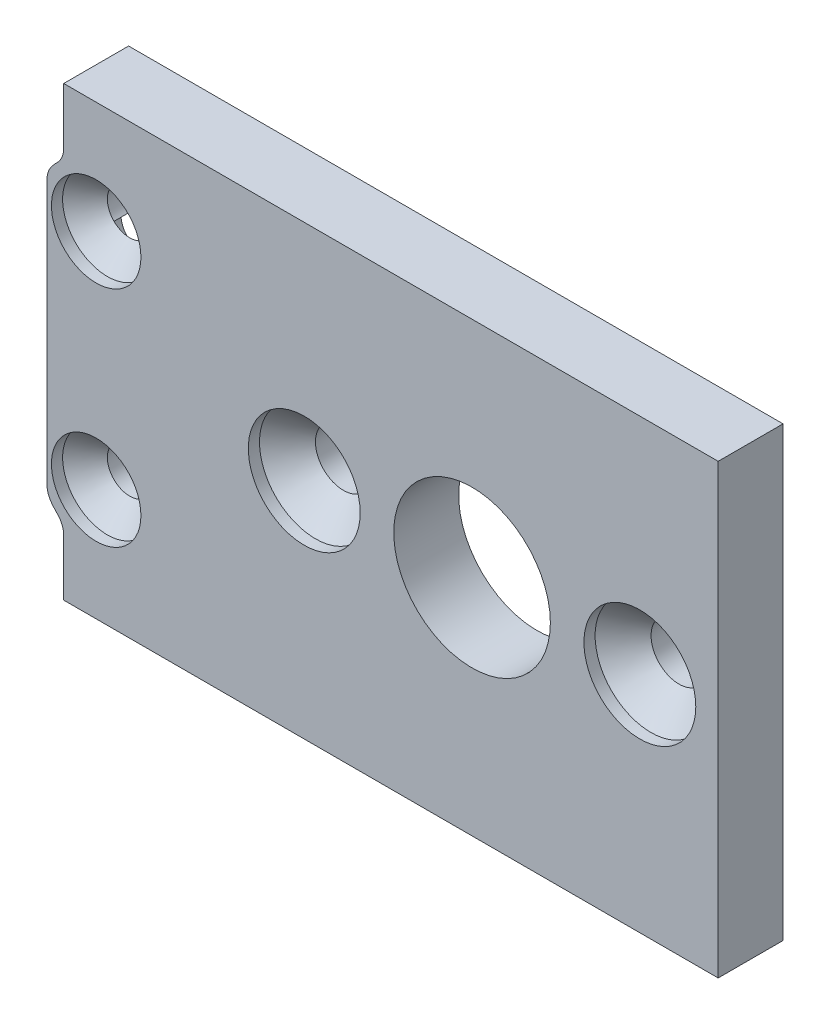
SolidWorks part; units mm, degrees
ref_plane "Front Plane" through (0, 0, 0) normal (0, 0, 1) x (1, 0, 0)
ref_plane "Top Plane" through (0, 0, 0) normal (0, 1, 0) x (1, 0, 0)
ref_plane "Right Plane" through (0, 0, 0) normal (1, 0, 0) x (0, 0, -1)
sketch "Sketch1" plane through (0, 0, 0) normal (0, 0, 1) x (1, 0, 0)
  line L1 (-92.5, 10) -> (92.5, 10)
  line L2 (-92.5, 10) -> (-92.5, -10)
  line L3 (-92.5, -10) -> (92.5, -10)
  line L4 (92.5, 10) -> (92.5, -10)
  line L5 (-92.5, 10) -> (92.5, -10) construction
  line L6 (-92.5, -10) -> (92.5, 10) construction
  point P0 (0, 0)
  dimension "D1" = 20
  dimension "D2" = 185
extrude "Base shape" add sketch "Sketch1" against normal blind 2.9
sketch "Sketch2" plane through (0, 0, 0) normal (0, 0, 1) x (1, 0, 0)
  line L0 (-83.5, 10) -> (-83.5, -10) construction
  line L1 (92.5, 10) -> (-92.5, 10) construction
  line L2 (-92.5, -10) -> (92.5, -10) construction
  line L3 (-92.5, 10) -> (-92.5, -10) construction
  line L4 (-92.5, 0) -> (92.5, 0) construction
  line L5 (92.5, -10) -> (92.5, 10) construction
  line L6 (-73.5, 10) -> (-73.5, -10) construction
  line L7 (0, 10) -> (0, -10) construction
  line L8 (73.5, 5) -> (92.5, 5) construction
  line L9 (-73.5, 3.5) -> (-92.5, 3.5) construction
  line L11 (80.5, -7) -> (66.5, -7)
  line L12 (80.5, -7) -> (80.5, 7)
  line L13 (80.5, 7) -> (66.5, 7)
  line L14 (66.5, -7) -> (66.5, 7)
  line L15 (80.5, -7) -> (66.5, 7) construction
  line L16 (80.5, 7) -> (66.5, -7) construction
  circle A0 centre (-73.5, 0) radius 10
  circle A1 centre (-81, 0) radius 1.25
  circle A2 centre (-66, 0) radius 1.25
  circle A3 centre (-73.5, 0) radius 3.5
  circle A4 centre (73.5, 0) radius 5
  circle A5 centre (66.5, 7) radius 1.25
  circle A6 centre (80.5, 7) radius 1.25
  circle A7 centre (80.5, -7) radius 1.25
  circle A8 centre (66.5, -7) radius 1.25
  dimension "D2" = 20
  dimension "D3" = 2.5
  dimension "D4" = 15
  dimension "D5" = 7
  dimension "D6" = 10
  dimension "D8" = 2.5
  dimension "D1" = 147
  dimension "D7" = 14
extrude "Motor cutouts" cut sketch "Sketch2" against normal up to next contours A5 | A6 | A7 | A8 | A1 | A2 | A3 | A4
hole_wizard "Motor M2.5 countersunks" positions "Sketch3" profile "Sketch4" countersink size "M2.5" standard "ANSI Metric" end condition through all
sketch "Sketch3" plane through (0, 0, 0) normal (0, 0, 1) x (1, 0, 0)
  point P0 (-81, 0)
  point P3 (-66, 0)
  point P7 (66.5, 7)
  point P10 (80.5, 7)
  point P13 (66.5, -7)
  point P16 (80.5, -7)
sketch "Sketch4" plane through (-81, 0, 0) normal (1, 0, 0) x (0, -1, 0)
  line L0 (0, 0) -> (0, 2.9)
  line L1 (0, 2.9) -> (1.25, 2.9)
  line L2 (1.25, 2.9) -> (1.25, 1.75)
  line L3 (1.25, 1.75) -> (2.5, 0.5)
  line L4 (2.5, 0.5) -> (2.5, 0)
  line L6 (2.5, 0) -> (0, 0)
  line L7 (-1.25, 1.75) -> (-2.5, 0.5) construction
  line L11 (0, -6.35) -> (0, 107.95) construction
  dimension "Thru Hole Dia." = 2.5
  dimension "Thru Hole Depth" = 2.9
  dimension "C'Sink Dia." = 5
  dimension "C'Sink Angle" = 90
  dimension "Head Clearance" = 0.5
sketch "Sketch5" plane through (0, 0, -2.9) normal (0, 0, -1) x (-1, 0, 0)
  line L0 (0, 10) -> (0, -10) construction
  line L3 (-92.5, 10) -> (92.5, 10) construction
  line L4 (92.5, -10) -> (-92.5, -10) construction
  line L5 (-60, -7) -> (60, -7) construction
  line L6 (-60, -6) -> (60, -6)
  line L7 (-60, -8) -> (60, -8)
  arc A0 (-60, -6) -> (-60, -8) centre (-60, -7) ccw
  arc A1 (60, -8) -> (60, -6) centre (60, -7) ccw
  point P8 (0, -7)
  dimension "D1" = 120
  dimension "D2" = 2
  dimension "D3" = 2
extrude "PCB slot" cut sketch "Sketch5" against normal blind 0.775
sketch "Sketch6" plane through (0, 0, 0) normal (0, 0, 1) x (1, 0, 0)
  line L0 (90.3, 10) -> (90.3, -10) construction
  line L1 (92.5, 10) -> (-92.5, 10) construction
  line L2 (-92.5, -10) -> (92.5, -10) construction
  line L3 (92.5, -10) -> (92.5, 10) construction
  line L4 (92.5, 0) -> (-92.5, 0) construction
  line L5 (-92.5, 10) -> (-92.5, -10) construction
  line L6 (0, 10) -> (0, -10) construction
  circle A0 centre (90.3, 5) radius 1
  circle A2 centre (90.3, -5) radius 1
  circle A3 centre (-90.3, -5) radius 1
  circle A5 centre (-90.3, 5) radius 1
  dimension "D2" = 2
  dimension "D1" = 2.2
  dimension "D3" = 10
extrude "End plate holes" cut sketch "Sketch6" against normal up to next
hole_wizard "CSK for M2 Flat Head Machine Screw3" positions "Sketch10" profile "Sketch9" countersink size "M2" standard "ANSI Metric" end condition through all
sketch "Sketch10" plane through (0, 0, 0) normal (0, 0, 1) x (1, 0, 0)
  point P2 (90.3, 5)
  point P8 (90.3, -5)
  point P11 (-90.3, 5)
  point P17 (-90.3, -5)
sketch "Sketch9" plane through (90.3, 5, 0) normal (1, 0, 0) x (0, -1, 0)
  line L0 (0, 0) -> (0, 2.9)
  line L1 (0, 2.9) -> (1, 2.9)
  line L2 (1, 2.9) -> (1, 1.5)
  line L3 (1, 1.5) -> (2, 0.5)
  line L4 (2, 0.5) -> (2, 0)
  line L6 (2, 0) -> (0, 0)
  line L7 (-1, 1.5) -> (-2, 0.5) construction
  line L11 (0, -6.35) -> (0, 107.95) construction
  dimension "Thru Hole Dia." = 2
  dimension "Thru Hole Depth" = 2.9
  dimension "C'Sink Dia." = 4
  dimension "C'Sink Angle" = 90
  dimension "Head Clearance" = 0.5
sketch "Sketch12" plane through (0, 0, -2.9) normal (0, 0, -1) x (-1, 0, 0)
  line L0 (-92.5, 0) -> (92.5, 0) construction
  line L1 (-92.5, -10) -> (-92.5, 10) construction
  line L2 (92.5, 10) -> (92.5, -10) construction
  line L3 (-90.3, 5) -> (-90.3, -5) construction
  line L4 (-88.8, 4) -> (-91.8, 1) construction
  line L5 (-91.8, 4) -> (-88.8, 4)
  line L6 (-91.8, 4) -> (-91.8, -4)
  line L7 (-91.8, -4) -> (-88.8, -4)
  line L8 (-88.8, 4) -> (-88.8, -4)
  line L9 (-91.8, 4) -> (-88.8, -4) construction
  line L10 (-91.8, -4) -> (-88.8, 4) construction
  line L11 (0, 10) -> (0, -10) construction
  line L12 (-92.5, 10) -> (92.5, 10) construction
  line L13 (92.5, -10) -> (-92.5, -10) construction
  line L14 (91.8, -4) -> (88.8, -4)
  line L15 (91.8, 4) -> (88.8, 4)
  line L16 (91.8, 4) -> (91.8, -4)
  line L17 (88.8, 4) -> (88.8, -4)
  circle A0 centre (-89.5071, 3.2929) radius 1
  circle A1 centre (-91.0929, 3.2929) radius 1
  circle A2 centre (-89.5071, -3.2929) radius 1
  circle A3 centre (-91.0929, -3.2929) radius 1
  circle A4 centre (89.5071, -3.2929) radius 1
  circle A5 centre (91.0929, -3.2929) radius 1
  circle A6 centre (89.5071, 3.2929) radius 1
  circle A7 centre (91.0929, 3.2929) radius 1
  point P10 (-90.3, 0)
  circle M9 centre (-90.3, -5) radius 1
  circle M10 centre (90.3, -5) radius 1
  circle M11 centre (90.3, 5) radius 1
  circle M12 centre (-90.3, 5) radius 1
  dimension "D3" = 2
  dimension "D1" = 3
  dimension "D2" = 8
  dimension "D4" = 45
extrude "Tap slots" cut sketch "Sketch12" against normal blind 1.4 contours A7 A6 M11 | A5 A4 M10 | A3 A2 M9 | A1 A0 M12 | A1 L5 M12 | A0 L5 M12 | A3 L7 M9 | A2 L7 M9 | A6 L15 M11 | A7 L15 M11 | A4 L14 M10 | A5 L14 M10 | A1 | A0 | A2 | A3 | L6 L7 L8 L5 | L17 L14 L16 L15 | A6 | A7 | A5 | A4 region at (90.3659, 4.0012, -2.9) region at (90.3, 5.03, -2.9) region at (90.2341, 4.0012, -2.9) region at (90.3659, -4.0012, -2.9) region at (90.3, -5.03, -2.9) region at (90.2341, -4.0012, -2.9) region at (-90.3659, -4.0012, -2.9) region at (-90.3, -5.03, -2.9) region at (-90.2341, -4.0012, -2.9) region at (-90.3659, 4.0012, -2.9) region at (-90.3, 5.03, -2.9) region at (-90.2341, 4.0012, -2.9)
sketch "Sketch13" plane through (0, 0, 0) normal (0, 0, 1) x (1, 0, 0)
  line L0 (-92.5, -10) -> (92.5, -10) construction
  line L1 (-92.5, 10) -> (-91.75, 10)
  line L2 (-92.5, 10) -> (-92.5, -10)
  line L3 (-92.5, -10) -> (-91.75, -10)
  line L4 (-91.75, 10) -> (-91.75, -10)
  line L5 (-92.5, 0) -> (92.5, 0) construction
  line L6 (92.5, -10) -> (92.5, 10) construction
  line L7 (0, 10) -> (0, -10) construction
  line L8 (92.5, 10) -> (-92.5, 10) construction
  line L9 (92.5, -10) -> (91.75, -10)
  line L10 (91.75, 10) -> (91.75, -10)
  line L11 (92.5, 10) -> (91.75, 10)
  line L12 (92.5, 10) -> (92.5, -10)
  circle A0 centre (-90.3, 5) radius 2.5
  circle A1 centre (-90.3, -5) radius 2.5
  circle A2 centre (90.3, 5) radius 2.5
  circle A3 centre (90.3, -5) radius 2.5
  line M16 (92.5, -10) -> (92.5, 10)
  line M17 (92.5, 10) -> (-92.5, 10)
  line M18 (-92.5, 10) -> (-92.5, -10)
  line M19 (-92.5, -10) -> (92.5, -10)
  dimension "D2" = 5
  dimension "D1" = 0.75
extrude "Cut-Extrude3" cut sketch "Sketch13" against normal up to next contours A0 L4 M17 M18 | A1 L4 M18 M19 | L10 A2 M16 M17 | A3 L10 M16 M19 region at (-92.1406, 8.3301, 0) region at (92.1406, 8.3301, 0) region at (-92.1406, -8.3301, 0) region at (92.1406, -8.3301, 0)
fillet "Fillet1" radius 1 8 edges at (-91.75, -7.0365, -1.45) (-92.5, -6.1874, -1.45) (-92.5, 6.1874, -1.45) (-91.75, 7.0365, -1.45) (92.5, 6.1874, -1.45) (91.75, 7.0365, -1.45) (92.5, -6.1874, -1.45) (91.75, -7.0365, -1.45)
sketch "Sketch14" plane through (0, 0, 0) normal (0, 0, 1) x (1, 0, 0)
  line L0 (-91.75, -10) -> (91.75, -10) construction
  line L1 (-62.5, -10) -> (92.5, -10)
  line L2 (-62.5, -10) -> (-62.5, 10)
  line L3 (-62.5, 10) -> (92.5, 10)
  line L4 (92.5, -10) -> (92.5, 10)
  line L5 (91.75, 10) -> (-91.75, 10) construction
  line L6 (92.5, -5.9) -> (92.5, 5.9) construction
  line L7 (-92.5, 5.9) -> (-92.5, -5.9) construction
  dimension "D1" = 30
extrude "Cut-Extrude4" cut sketch "Sketch14" against normal up to next
